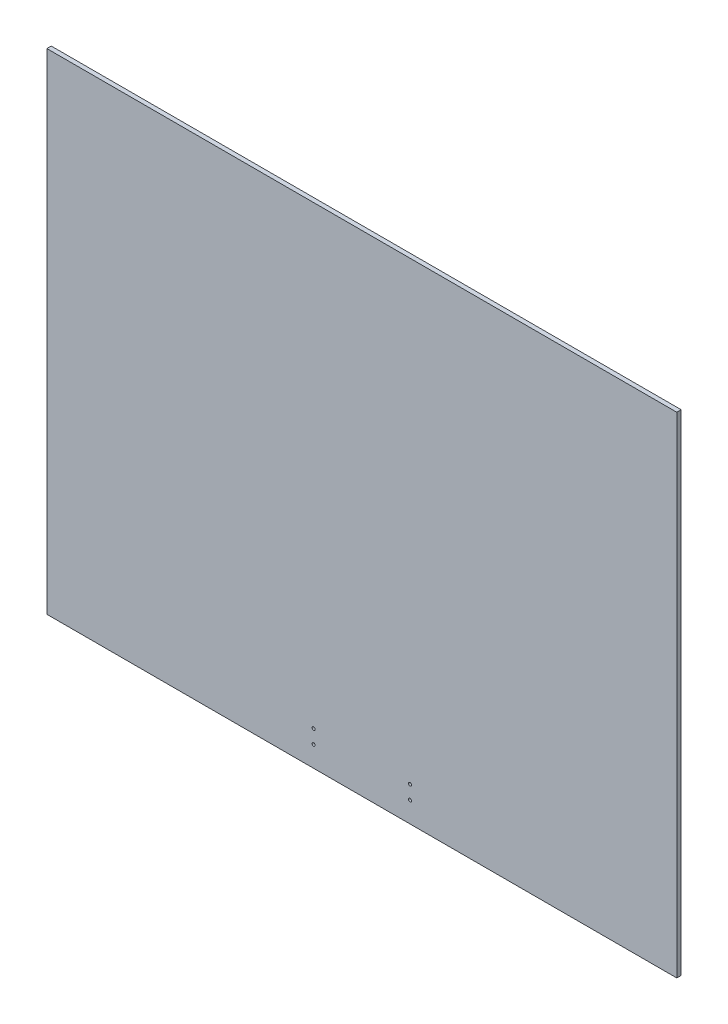
SolidWorks part; units mm, degrees
ref_plane "Front Plane" through (0, 0, 0) normal (0, 0, 1) x (1, 0, 0)
ref_plane "Top Plane" through (0, 0, 0) normal (0, 1, 0) x (1, 0, 0)
ref_plane "Right Plane" through (0, 0, 0) normal (1, 0, 0) x (0, 0, -1)
sketch "Sketch1" plane through (0, 0, 0) normal (0, 0, 1) x (1, 0, 0)
  line L1 (-457.2, -355.6) -> (457.2, -355.6)
  line L2 (-457.2, -355.6) -> (-457.2, 355.6)
  line L3 (-457.2, 355.6) -> (457.2, 355.6)
  line L4 (457.2, -355.6) -> (457.2, 355.6)
  line L5 (-457.2, -355.6) -> (457.2, 355.6) construction
  line L6 (-457.2, 355.6) -> (457.2, -355.6) construction
  point P0 (0, 0)
  dimension "D1" = 914.4
  dimension "D2" = 711.2
extrude "Boss-Extrude1" add sketch "Sketch1" along normal blind 6.35
sketch "Sketch2" plane through (0, 0, 6.35) normal (0, 0, 1) x (1, 0, 0)
  line L4 (457.2, -355.6) -> (457.2, 355.6)
  line L5 (457.2, 355.6) -> (-457.2, 355.6)
  line L6 (-457.2, 355.6) -> (-457.2, -355.6)
  line L7 (-457.2, -355.6) -> (457.2, -355.6)
  line L8 (457.2, -355.6) -> (457.2, 355.6)
  line L9 (457.2, 355.6) -> (-457.2, 355.6)
  line L10 (-457.2, 355.6) -> (-457.2, -355.6)
  line L11 (-457.2, -355.6) -> (457.2, -355.6)
  circle A0 centre (70, -305.6) radius 2.2 construction
  circle A1 centre (70, -325.6) radius 2.2 construction
  circle A2 centre (-70, -325.6) radius 2.2 construction
  circle A3 centre (-70, -305.6) radius 2.2 construction
  circle A4 centre (70, -305.6) radius 2.2
  circle A5 centre (70, -325.6) radius 2.2
  circle A6 centre (-70, -325.6) radius 2.2
  circle A7 centre (-70, -305.6) radius 2.2
  dimension "D1" = 0
extrude "Cut-Extrude2" cut sketch "Sketch2" against normal through all contours A4 | A5 | A7 | A6 region at (70, -305.6, 6.35) region at (70, -325.6, 6.35) region at (-70, -325.6, 6.35) region at (-70, -305.6, 6.35)
